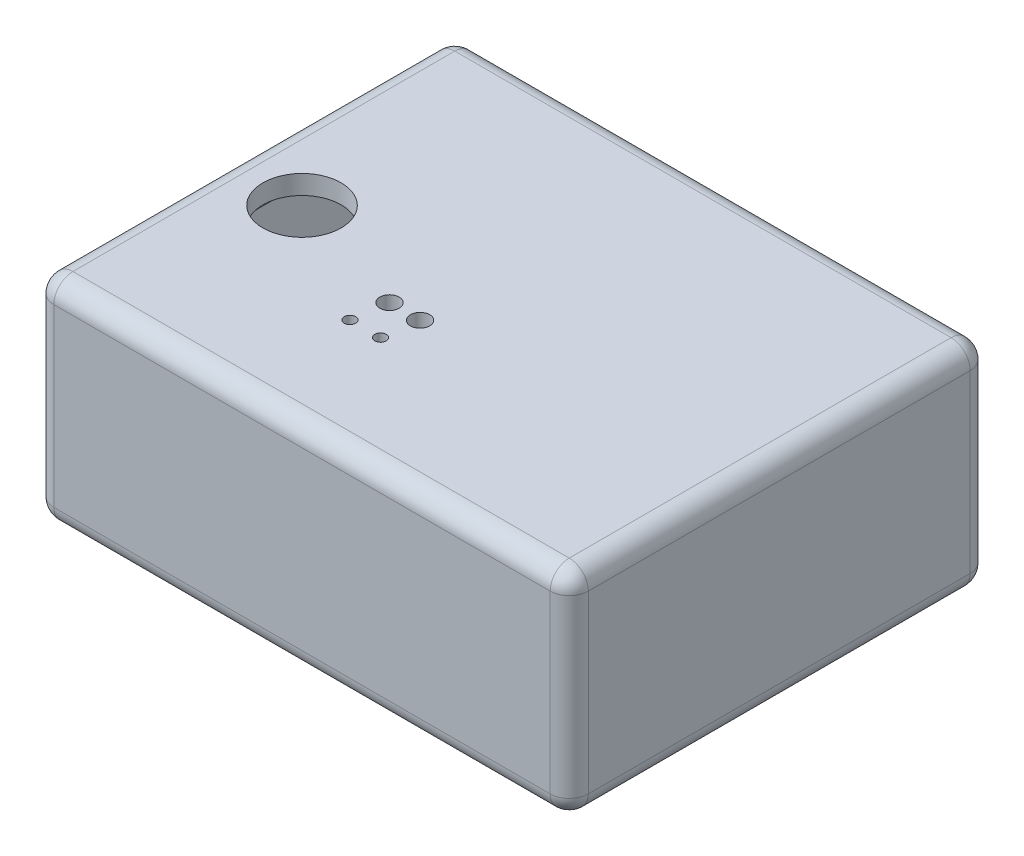
SolidWorks part; units mm, degrees
ref_plane "Front Plane" through (0, 0, 0) normal (0, 0, 1) x (1, 0, 0)
ref_plane "Top Plane" through (0, 0, 0) normal (0, 1, 0) x (1, 0, 0)
ref_plane "Right Plane" through (0, 0, 0) normal (1, 0, 0) x (0, 0, -1)
sketch "Sketch1" plane through (0, 0, 0) normal (0, 1, 0) x (1, 0, 0)
  line L1 (-70, -55) -> (70, -55)
  line L2 (-70, -55) -> (-70, 55)
  line L3 (-70, 55) -> (70, 55)
  line L4 (70, -55) -> (70, 55)
  line L5 (-70, -55) -> (70, 55) construction
  line L6 (-70, 55) -> (70, -55) construction
  point P0 (0, 0)
  dimension "D1" = 140
  dimension "D2" = 110
extrude "Boss-Extrude1" add sketch "Sketch1" along normal blind 56
sketch "Sketch2" plane through (0, 0, 0) normal (0, -1, 0) x (1, 0, 0)
  line L0 (-70, -55) -> (-70, 55) construction
  line L1 (-65, -50) -> (65, -50)
  line L2 (-65, -50) -> (-65, 50)
  line L3 (-65, 50) -> (65, 50)
  line L4 (65, -50) -> (65, 50)
  line L5 (-65, -50) -> (65, 50) construction
  line L6 (-65, 50) -> (65, -50) construction
  line L7 (-70, 55) -> (70, 55) construction
  point P0 (0, 0)
  dimension "D1" = 5
  dimension "D2" = 5
extrude "Cut-Extrude1" cut sketch "Sketch2" against normal blind 51
fillet "Fillet1" radius 5 4 edges at (0, 56, -55) (70, 56, 0) (0, 56, 55) (-70, 56, 0)
fillet "Fillet2" radius 5 8 edges at (-70, 25.5, -55) (70, 25.5, -55) (70, 25.5, 55) (-70, 25.5, 55) (-68.5355, 54.5355, -53.5355) (68.5355, 54.5355, -53.5355) (68.5355, 54.5355, 53.5355) (-68.5355, 54.5355, 53.5355)
fillet "Fillet3" radius 5 4 edges at (65, 51, 0) (0, 51, -50) (-65, 51, 0) (0, 51, 50)
fillet "Fillet4" radius 5 8 edges at (65, 23, 50) (65, 23, -50) (-65, 23, -50) (-65, 23, 50) (63.5355, 49.5355, 48.5355) (63.5355, 49.5355, -48.5355) (-63.5355, 49.5355, -48.5355) (-63.5355, 49.5355, 48.5355)
fillet "Fillet6" radius 5 8 edges at (-68.5355, 0, 53.5355) (-70, 0, 0) (-68.5355, 0, -53.5355) (0, 0, -55) (68.5355, 0, -53.5355) (70, 0, 0) (68.5355, 0, 53.5355) (0, 0, 55)
sketch "Sketch3" plane through (0, 56, 0) normal (0, 1, 0) x (1, 0, 0)
  line L0 (-70, -50) -> (-70, 50) construction
  line L1 (65, -55) -> (-65, -55) construction
  circle A0 centre (-16.48, -15.61) radius 2.54
  circle A1 centre (-8.48, -15.61) radius 2.54
  dimension "D1" = 8
  dimension "D2" = 53.52
  dimension "D3" = 39.39
extrude "Cut-Extrude2" cut sketch "Sketch3" against normal blind 5
sketch "Sketch4" plane through (0, 56, 0) normal (0, 1, 0) x (1, 0, 0)
  line L0 (-65, 50) -> (-65, -50) construction
  line L2 (65, -55) -> (-65, -55) construction
  circle A0 centre (-50, -5) radius 10.25
  dimension "D1" = 20.5
  dimension "D2" = 15
  dimension "D3" = 50
extrude "Cut-Extrude3" cut sketch "Sketch4" against normal blind 5
sketch "Sketch5" plane through (0, 56, 0) normal (0, 1, 0) x (1, 0, 0)
  line L0 (-70, -50) -> (-70, 50) construction
  line L1 (65, -55) -> (-65, -55) construction
  circle A0 centre (-17.725, -24.71) radius 1.5
  circle A1 centre (-9.725, -24.71) radius 1.5
  dimension "D1" = 52.275
  dimension "D2" = 8
  dimension "D3" = 30.29
  dimension "D4" = 30.29
extrude "Cut-Extrude4" cut sketch "Sketch5" against normal blind 5
